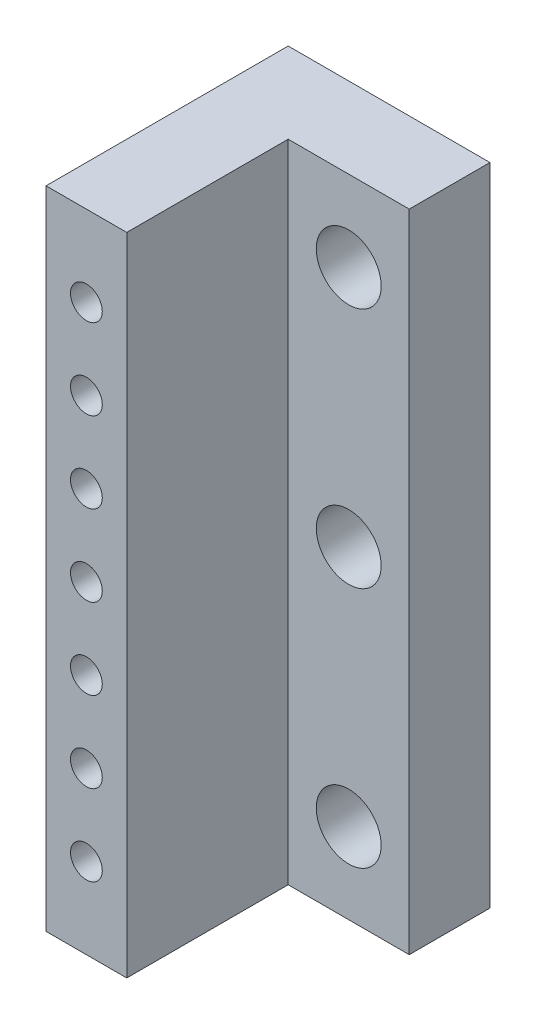
SolidWorks part; units mm, degrees
material "6061-T6 (SS)"
ref_plane "Front" through (0, 0, 0) normal (0, 0, 1) x (1, 0, 0)
ref_plane "Top" through (0, 0, 0) normal (0, 1, 0) x (1, 0, 0)
ref_plane "Right" through (0, 0, 0) normal (1, 0, 0) x (0, 0, -1)
sketch "Sketch1" plane through (0, 0, 0) normal (0, 1, 0) x (1, 0, 0)
  line L0 (0, 0) -> (0, -19.05)
  line L1 (0, -19.05) -> (6.35, -19.05)
  line L2 (6.35, -19.05) -> (6.35, -6.35)
  line L3 (6.35, -6.35) -> (15.875, -6.35)
  line L4 (15.875, -6.35) -> (15.875, 0)
  line L5 (15.875, 0) -> (0, 0)
  dimension "D1" = 6.35
  dimension "D2" = 19.05
  dimension "D3" = 15.875
  dimension "D4" = 6.35
extrude "Boss-Extrude1" add sketch "Sketch1" along normal blind 50.8
sketch "Sketch4" plane through (0, 0, 19.05) normal (0, 0, 1) x (1, 0, 0)
  line L0 (0, 0) -> (6.35, 0) construction
  line L1 (0, 0) -> (3.175, 6.35) construction
  line L2 (3.175, 6.35) -> (6.35, 0) construction
  point P0 (3.175, 6.35)
  point P16 (3.175, 12.7)
  point P17 (3.175, 19.05)
  point P18 (3.175, 25.4)
  point P19 (3.175, 31.75)
  point P20 (3.175, 38.1)
  point P21 (3.175, 44.45)
  dimension "D1" = 6.35
  dimension "D3" = 6.35
  dimension "D2" = 7
hole_wizard "M3x0.5 Tapped Hole1" positions "Sketch4" profile "Sketch3" tap size "M3x0.5" standard "ANSI Metric"
sketch "Sketch3" plane through (3.175, 6.35, 19.05) normal (1, 0, 0) x (0, -1, 0)
  line L0 (0, 0) -> (0, 8.2441)
  line L1 (0, 8.2441) -> (1.25, 7.493)
  line L2 (1.25, 7.493) -> (1.25, 0)
  line L5 (1.25, 0) -> (0, 0)
  line L10 (0, 8.2441) -> (-1.25, 7.493) construction
  line L11 (0, -6.35) -> (0, 107.95) construction
  dimension "Tap Drill Dia." = 2.5
  dimension "Tap Drill Depth" = 7.493
  dimension "Drill Angle" = 118
cosmetic thread "Hole Thread1" parameters "D1"=5.9944, "D2"=3
cosmetic thread "Hole Thread2" parameters "D1"=5.9944, "D2"=3
cosmetic thread "Hole Thread3" parameters "D1"=5.9944, "D2"=3
cosmetic thread "Hole Thread4" parameters "D1"=5.9944, "D2"=3
cosmetic thread "Hole Thread5" parameters "D1"=5.9944, "D2"=3
cosmetic thread "Hole Thread6" parameters "D1"=5.9944, "D2"=3
cosmetic thread "Hole Thread7" parameters "D1"=5.9944, "D2"=3
sketch "Sketch7" plane through (0, 0, 6.35) normal (0, 0, 1) x (1, 0, 0)
  line L1 (11.1125, 44.45) -> (11.1125, 6.35) construction
  line L3 (6.35, 0) -> (15.875, 0) construction
  line L4 (6.35, 50.8) -> (15.875, 50.8) construction
  line L5 (15.875, 50.8) -> (15.875, 0) construction
  point P0 (11.1125, 6.35)
  point P2 (11.1125, 25.4)
  point P4 (11.1125, 44.45)
  dimension "D1" = 6.35
  dimension "D2" = 6.35
  dimension "D3" = 19.05
  dimension "D4" = 4.7625
hole_wizard "#10 Clearance Hole1" positions "Sketch7" profile "Sketch6" hole size "#10" standard "ANSI Inch" end condition up to next
sketch "Sketch6" plane through (11.1125, 6.35, 6.35) normal (1, 0, 0) x (0, -1, 0)
  line L0 (0, 0) -> (0, 6.35)
  line L1 (0, 6.35) -> (2.5527, 6.35)
  line L2 (2.5527, 6.35) -> (2.5527, 0)
  line L5 (2.5527, 0) -> (0, 0)
  line L11 (0, -6.35) -> (0, 107.95) construction
  dimension "Thru Hole Dia." = 5.1054
  dimension "Thru Hole Depth" = 6.35
